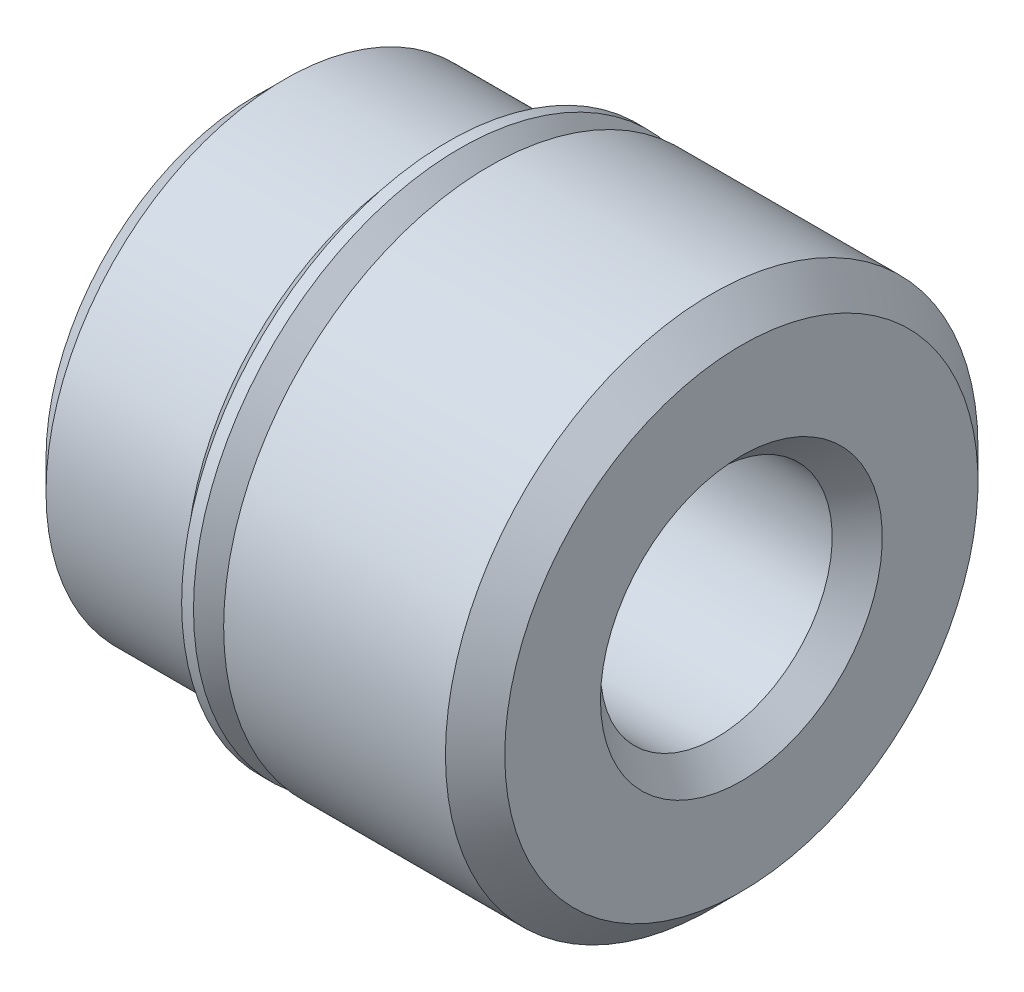
SolidWorks part; units mm, degrees
ref_plane "Front Plane" through (0, 0, 0) normal (0, 0, 1) x (1, 0, 0)
ref_plane "Top Plane" through (0, 0, 0) normal (0, 1, 0) x (1, 0, 0)
ref_plane "Right Plane" through (0, 0, 0) normal (1, 0, 0) x (0, 0, -1)
sketch "Sketch1" plane through (0, 0, 0) normal (0, 0, 1) x (1, 0, 0)
  line L0 (0, 0) -> (0, 3.5751)
  line L1 (0, 3.5751) -> (0.508, 4.0831)
  line L2 (0.508, 4.0831) -> (2.9083, 4.0831)
  line L3 (2.9083, 4.0831) -> (3.4671, 3.5242)
  line L4 (3.4671, 3.5242) -> (4.0259, 3.5242)
  line L5 (4.0259, 3.5242) -> (4.0259, 4.5593)
  line L6 (4.0259, 4.5593) -> (7.8232, 4.5593)
  line L7 (7.8232, 4.5593) -> (8.3312, 4.0513)
  line L8 (8.3312, 4.0513) -> (8.3312, 0)
  line L9 (8.3312, 0) -> (0, 0)
  line L10 (8.3312, 0) -> (0, 0) construction
revolve "Revolve1" add sketch "Sketch1" angle 360 about L10 reverse direction yes
sketch "Sketch2" plane through (0, 0, 0) normal (0, 0, 1) x (1, 0, 0)
  line L0 (0, 0) -> (0, 2.413)
  line L1 (0, 2.413) -> (0.4293, 1.9837)
  line L2 (0.4293, 1.9837) -> (7.9019, 1.9837)
  line L3 (7.9019, 1.9837) -> (8.3312, 2.413)
  line L4 (8.3312, 2.413) -> (8.3312, 0)
  line L5 (8.3312, 0) -> (0, 0)
  line L6 (8.3312, 0) -> (0, 0) construction
revolve "Cut-Revolve1" cut sketch "Sketch2" angle 360 about L6 reverse direction yes
cosmetic thread "Cosmetic Thread1" parameters "D1"=8.3312, "D2"=4.826
ref_plane "Plane1" through (8.3312, 0, 0) normal (1, 0, 0) x (0, 0, -1)
ref_plane "Plane2" through (13.5509, 0, 0) normal (1, 0, 0) x (0, 0, -1)
ref_plane "Plane3" through (0, 0, 0) normal (0, 0.9998, 0.0175) x (1, 0, 0)
ref_plane "Plane4" through (9.525, 0, 0) normal (1, 0, 0) x (0, 0, -1)
ref_plane "Plane5" through (3.4671, 0, 0) normal (1, 0, 0) x (0, 0, -1)
sketch "Sketch3" plane through (0, 0, 0) normal (0, 0, 1) x (1, 0, 0)
  line L0 (3.3065, 4.4751) -> (3.9121, 3.8695)
  line L1 (3.9121, 3.6899) -> (3.7465, 3.5242)
  line L2 (3.7465, 3.5242) -> (3.4671, 3.5242)
  line L3 (3.4671, 3.5242) -> (3.4671, 3.2702)
  line L4 (3.4671, 3.2702) -> (4.0259, 3.2703)
  line L5 (4.0259, 3.2703) -> (4.0259, 4.0431)
  line L6 (4.0259, 4.0431) -> (3.5097, 4.5593)
  line L7 (3.5097, 4.5593) -> (3.3065, 4.5593)
  line L8 (3.3065, 4.5593) -> (3.3065, 4.4751)
  line L9 (4.0259, 0) -> (3.4671, 0) construction
  arc A0 (3.9121, 3.8695) -> (3.9121, 3.6899) centre (3.8223, 3.7797) cw
revolve "Revolve2" add sketch "Sketch3" angle 360 about L9 reverse direction yes
ref_plane "Plane6" through (8.4582, 0, 0) normal (1, 0, 0) x (0, 0, -1)
ref_plane "Plane7" through (0, 0, 0) normal (1, 0, 0) x (0, 0, -1)
ref_plane "Plane8" through (8.3312, 0, 0) normal (1, 0, 0) x (0, 0, -1)
ref_plane "Plane9" through (8.3312, 0, 0) normal (1, 0, 0) x (0, 0, -1)
ref_plane "Plane10" through (0, 0, 0) normal (0, 1, 0) x (1, 0, 0)
ref_plane "Plane11" through (0, 0, 0) normal (0, 1, 0) x (1, 0, 0)
ref_plane "Plane12" through (13.5509, 0, 0) normal (1, 0, 0) x (0, 0, -1)
ref_plane "lovra XY" through (8.3312, 0, 0) normal (1, 0, 0) x (0, 0, -1)
ref_plane "lovra XZ" through (0, 0, 0) normal (0, 0, -1) x (-1, 0, 0)
ref_plane "lovra YZ" through (0, 0, 0) normal (0, 1, 0) x (1, 0, 0)
ref_axis "lovra X" through (8.3312, -50, 0) along (0, 1, 0)
ref_axis "lovra Y" through (8.3312, 0, -80.9) along (0, 0, 1)
ref_axis "lovra Z" through (80.9, 0, 0) along (-1, 0, 0)
sketch3d "lovra"
  point P0 (8.3312, 0, 0)
ref_plane "lovra1 XY" through (8.3312, 0, 0) normal (1, 0, 0) x (0, 0, -1)
ref_plane "lovra1 XZ" through (0, 0, 0) normal (0, -1, 0) x (-1, 0, 0)
ref_plane "lovra1 YZ" through (0, 0, 0) normal (0, 0, -1) x (-1, 0, 0)
ref_axis "lovra1 X" through (8.3312, 0, 80.9) along (0, 0, -1)
ref_axis "lovra1 Y" through (8.3312, -50, 0) along (0, 1, 0)
ref_axis "lovra1 Z" through (80.9, 0, 0) along (-1, 0, 0)
sketch3d "lovra1"
  point P0 (8.3312, 0, 0)
ref_plane "lovra2 XY" through (8.3312, 0, 0) normal (1, 0, 0) x (0, 0, -1)
ref_plane "lovra2 XZ" through (0, 0, 0) normal (0, -1, 0) x (-1, 0, 0)
ref_plane "lovra2 YZ" through (0, 0, 0) normal (0, 0, -1) x (-1, 0, 0)
ref_axis "lovra2 X" through (8.3312, 0, 80.9) along (0, 0, -1)
ref_axis "lovra2 Y" through (8.3312, -50, 0) along (0, 1, 0)
ref_axis "lovra2 Z" through (80.9, 0, 0) along (-1, 0, 0)
sketch3d "lovra2"
  point P0 (8.3312, 0, 0)
ref_plane "lovra21 XY" through (0, 0, 0) normal (1, 0, 0) x (0, 0, -1)
ref_plane "lovra21 XZ" through (0, 0, 0) normal (0, -1, 0) x (-1, 0, 0)
ref_plane "lovra21 YZ" through (0, 0, 5.2705) normal (0, 0, -1) x (-1, 0, 0)
ref_axis "lovra21 X" through (0, 0, 80.9) along (0, 0, -1)
ref_axis "lovra21 Y" through (0, -50, 5.2705) along (0, 1, 0)
ref_axis "lovra21 Z" through (80.9, 0, 5.2705) along (-1, 0, 0)
sketch3d "lovra21"
  point P0 (0, 0, 5.2705)
ref_plane "lovra22 XY" through (0, 0, 0) normal (1, 0, 0) x (0, 0, -1)
ref_plane "lovra22 XZ" through (0, 0, 0) normal (0, -1, 0) x (-1, 0, 0)
ref_plane "lovra22 YZ" through (0, 0, -5.2705) normal (0, 0, -1) x (-1, 0, 0)
ref_axis "lovra22 X" through (0, 0, 80.9) along (0, 0, -1)
ref_axis "lovra22 Y" through (0, -50, -5.2705) along (0, 1, 0)
ref_axis "lovra22 Z" through (80.9, 0, -5.2705) along (-1, 0, 0)
sketch3d "lovra22"
  point P0 (0, 0, -5.2705)
ref_plane "lovra3 XY" through (8.3312, 0, 0) normal (1, 0, 0) x (0, 0, -1)
ref_plane "lovra3 XZ" through (0, 0, 0) normal (0, -1, 0) x (-1, 0, 0)
ref_plane "lovra3 YZ" through (0, 0, 0) normal (0, 0, -1) x (-1, 0, 0)
ref_axis "lovra3 X" through (8.3312, 0, 80.9) along (0, 0, -1)
ref_axis "lovra3 Y" through (8.3312, -50, 0) along (0, 1, 0)
ref_axis "lovra3 Z" through (80.9, 0, 0) along (-1, 0, 0)
sketch3d "lovra3"
  point P0 (8.3312, 0, 0)
ref_plane "olen XY" through (8.3312, 0, 0) normal (1, 0, 0) x (0, 0, -1)
ref_plane "olen XZ" through (0, 0, 0) normal (0, -1, 0) x (-1, 0, 0)
ref_plane "olen YZ" through (0, 0, 0) normal (0, 0, -1) x (-1, 0, 0)
ref_axis "olen X" through (8.3312, 0, 80.9) along (0, 0, -1)
ref_axis "olen Y" through (8.3312, -50, 0) along (0, 1, 0)
ref_axis "olen Z" through (80.9, 0, 0) along (-1, 0, 0)
sketch3d "olen"
  point P0 (8.3312, 0, 0)
ref_plane "to_mounting_bracket XY" through (13.5509, 0, 0) normal (1, 0, 0) x (0, 0, -1)
ref_plane "to_mounting_bracket XZ" through (0, 0, 0) normal (0, -1, 0) x (-1, 0, 0)
ref_plane "to_mounting_bracket YZ" through (0, 0, 0) normal (0, 0, -1) x (-1, 0, 0)
ref_axis "to_mounting_bracket X" through (13.5509, 0, 80.9) along (0, 0, -1)
ref_axis "to_mounting_bracket Y" through (13.5509, -50, 0) along (0, 1, 0)
ref_axis "to_mounting_bracket Z" through (80.9, 0, 0) along (-1, 0, 0)
sketch3d "to_mounting_bracket"
  point P0 (13.5509, 0, 0)
ref_plane "to_nut XY" through (0, 0, 0) normal (1, 0, 0) x (0, 0, -1)
ref_plane "to_nut XZ" through (0, 0, 0) normal (0, -1, 0) x (-1, 0, 0)
ref_plane "to_nut YZ" through (0, 0, 0) normal (0, 0, -1) x (-1, 0, 0)
ref_axis "to_nut X" through (0, 0, 80.9) along (0, 0, -1)
ref_axis "to_nut Y" through (0, -50, 0) along (0, 1, 0)
ref_axis "to_nut Z" through (80.9, 0, 0) along (-1, 0, 0)
sketch3d "to_nut"
  point P0 (0, 0, 0)
ref_plane "to_pin XY" through (0, 0, 0) normal (0, 0, 1) x (1, 0, 0)
ref_plane "to_pin XZ" through (0, 0, 0) normal (0, -1, 0) x (-1, 0, 0)
ref_plane "to_pin YZ" through (18.2626, 0, 0) normal (1, 0, 0) x (0, 0, -1)
ref_axis "to_pin X" through (-80.9, 0, 0) along (1, 0, 0)
ref_axis "to_pin Y" through (18.2626, -50, 0) along (0, 1, 0)
ref_axis "to_pin Z" through (18.2626, 0, 80.9) along (0, 0, -1)
sketch3d "to_pin"
  point P0 (18.2626, 0, 0)
ref_plane "to_screw XY" through (0, 0, 0) normal (0, 1, 0) x (1, 0, 0)
ref_plane "to_screw XZ" through (0, 0, 0) normal (0, 0, 1) x (1, 0, 0)
ref_plane "to_screw YZ" through (9.525, 0, 0) normal (1, 0, 0) x (0, 0, -1)
ref_axis "to_screw X" through (-80.9, 0, 0) along (1, 0, 0)
ref_axis "to_screw Y" through (9.525, 0, 50) along (0, 0, -1)
ref_axis "to_screw Z" through (9.525, 50, 0) along (0, -1, 0)
sketch3d "to_screw"
  point P0 (9.525, 0, 0)
ref_plane "to_tube XY" through (3.4671, 0, 0) normal (1, 0, 0) x (0, 0, -1)
ref_plane "to_tube XZ" through (0, 0, 0) normal (0, -1, 0) x (-1, 0, 0)
ref_plane "to_tube YZ" through (0, 0, 0) normal (0, 0, -1) x (-1, 0, 0)
ref_axis "to_tube X" through (3.4671, 0, 80.9) along (0, 0, -1)
ref_axis "to_tube Y" through (3.4671, -50, 0) along (0, 1, 0)
ref_axis "to_tube Z" through (80.9, 0, 0) along (-1, 0, 0)
sketch3d "to_tube"
  point P0 (3.4671, 0, 0)
